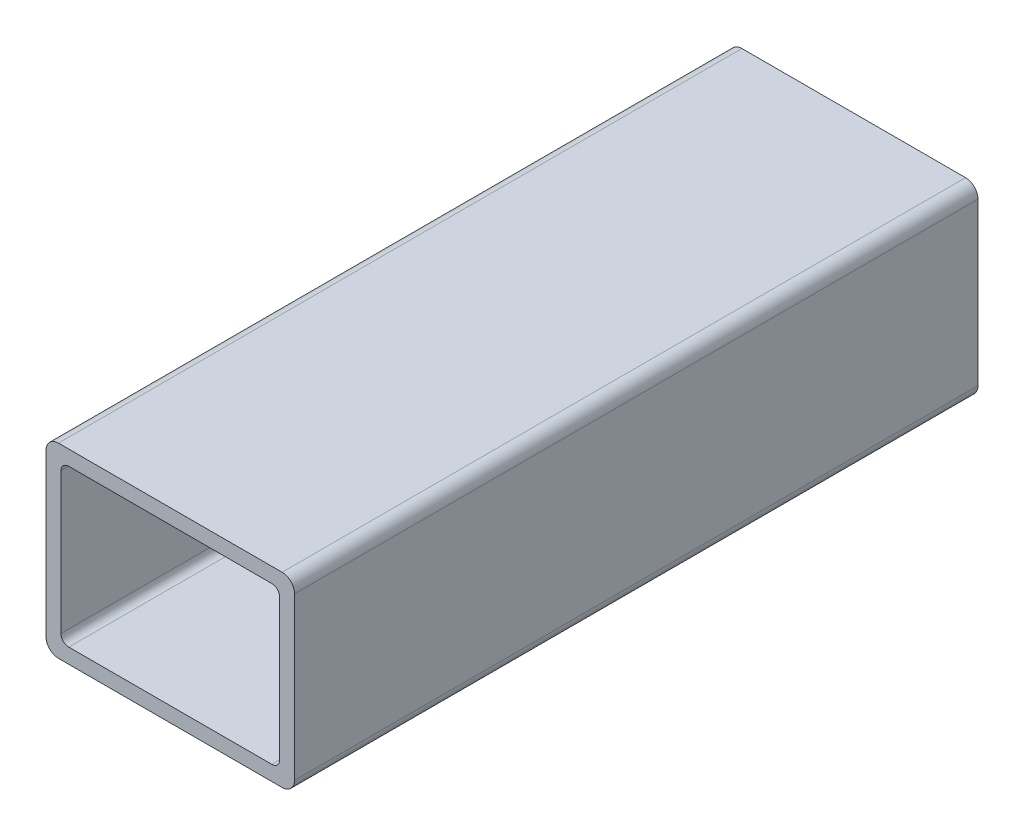
SolidWorks part; units mm, degrees
material "Plain Carbon Steel"
ref_plane "Front" through (0, 0, 0) normal (0, 0, 1) x (1, 0, 0)
ref_plane "Top" through (0, 0, 0) normal (0, 1, 0) x (1, 0, 0)
ref_plane "Right" through (0, 0, 0) normal (1, 0, 0) x (0, 0, -1)
sketch "Sketch1" plane through (0, 0, 0) normal (0, 0, 1) x (1, 0, 0)
  line L0 (-22.352, 0) -> (-25.4, 0) construction
  line L1 (22.86, -19.05) -> (-22.86, -19.05)
  line L2 (25.4, -16.51) -> (25.4, 16.51)
  line L3 (22.86, 19.05) -> (-22.86, 19.05)
  line L4 (-25.4, -16.51) -> (-25.4, 16.51)
  line L5 (25.4, -19.05) -> (-25.4, 19.05) construction
  line L6 (25.4, 19.05) -> (-25.4, -19.05) construction
  line L7 (20.7518, 16.002) -> (-20.7518, 16.002)
  line L8 (22.352, 14.4018) -> (22.352, -14.4018)
  line L9 (20.7518, -16.002) -> (-20.7518, -16.002)
  line L10 (-22.352, 14.4018) -> (-22.352, -14.4018)
  line L11 (22.352, 16.002) -> (-22.352, -16.002) construction
  line L12 (22.352, -16.002) -> (-22.352, 16.002) construction
  line L13 (0, -16.002) -> (0, -19.05) construction
  line L14 (22.352, -14.4018) -> (22.352, -19.05) construction
  line L16 (22.352, -19.05) -> (25.4, -19.05) construction
  arc A0 (-20.7518, -16.002) -> (-22.352, -14.4018) centre (-20.7518, -14.4018) cw
  arc A1 (22.352, -14.4018) -> (20.7518, -16.002) centre (20.7518, -14.4018) cw
  arc A2 (20.7518, 16.002) -> (22.352, 14.4018) centre (20.7518, 14.4018) cw
  arc A3 (-20.7518, 16.002) -> (-22.352, 14.4018) centre (-20.7518, 14.4018) ccw
  arc A4 (22.86, -19.05) -> (25.4, -16.51) centre (22.86, -16.51) ccw
  arc A5 (25.4, 16.51) -> (22.86, 19.05) centre (22.86, 16.51) ccw
  arc A6 (-22.86, 19.05) -> (-25.4, 16.51) centre (-22.86, 16.51) ccw
  arc A7 (-22.86, -19.05) -> (-25.4, -16.51) centre (-22.86, -16.51) cw
  point P0 (0, 0)
  point P6 (0, 0)
  dimension "D2" = 1.6002
  dimension "D3" = 2.54
sketch "Sketch2" plane through (0, 0, 0) normal (1, 0, 0) x (0, 0, -1)
  line L0 (-152.4, 0) -> (152.4, 0) construction
  dimension "Length" = 304.8
ref_plane "Plane1" through (25.4, 0, 0) normal (1, 0, 0) x (0, 0, -1)
sketch "Sketch5" plane through (25.4, 0, 0) normal (1, 0, 0) x (0, 0, -1)
  line L0 (-152.4, 19.05) -> (-152.4, -19.05) construction
  line L1 (152.4, 19.05) -> (152.4, -19.05) construction
sketch "Sketch4" plane through (0, 0, 0) normal (0, 0, 1) x (1, 0, 0)
  line L0 (25.4, -16.51) -> (25.4, 16.51) construction
  line L1 (22.86, 19.05) -> (-22.86, 19.05) construction
  line L2 (-25.4, -16.51) -> (-25.4, 16.51) construction
  line L3 (22.86, -19.05) -> (-22.86, -19.05) construction
  line L4 (22.352, 14.4018) -> (22.352, -14.4018) construction
  line L5 (20.7518, -16.002) -> (-20.7518, -16.002) construction
  line L6 (-22.352, 14.4018) -> (-22.352, -14.4018) construction
  line L7 (20.7518, 16.002) -> (-20.7518, 16.002) construction
  line L8 (25.4, -16.51) -> (25.4, 16.51)
  line L9 (22.86, 19.05) -> (-22.86, 19.05)
  line L10 (-25.4, -16.51) -> (-25.4, 16.51)
  line L11 (22.86, -19.05) -> (-22.86, -19.05)
  line L12 (22.352, 14.4018) -> (22.352, -14.4018)
  line L13 (20.7518, -16.002) -> (-20.7518, -16.002)
  line L14 (-22.352, 14.4018) -> (-22.352, -14.4018)
  line L15 (20.7518, 16.002) -> (-20.7518, 16.002)
  arc A0 (25.4, 16.51) -> (22.86, 19.05) centre (22.86, 16.51) ccw construction
  arc A1 (-22.86, 19.05) -> (-25.4, 16.51) centre (-22.86, 16.51) ccw construction
  arc A2 (-25.4, -16.51) -> (-22.86, -19.05) centre (-22.86, -16.51) ccw construction
  arc A3 (22.86, -19.05) -> (25.4, -16.51) centre (22.86, -16.51) ccw construction
  arc A4 (20.7518, -16.002) -> (22.352, -14.4018) centre (20.7518, -14.4018) ccw construction
  arc A5 (-22.352, -14.4018) -> (-20.7518, -16.002) centre (-20.7518, -14.4018) ccw construction
  arc A6 (-20.7518, 16.002) -> (-22.352, 14.4018) centre (-20.7518, 14.4018) ccw construction
  arc A7 (22.352, 14.4018) -> (20.7518, 16.002) centre (20.7518, 14.4018) ccw construction
  arc A8 (25.4, 16.51) -> (22.86, 19.05) centre (22.86, 16.51) ccw
  arc A9 (-22.86, 19.05) -> (-25.4, 16.51) centre (-22.86, 16.51) ccw
  arc A10 (-25.4, -16.51) -> (-22.86, -19.05) centre (-22.86, -16.51) ccw
  arc A11 (22.86, -19.05) -> (25.4, -16.51) centre (22.86, -16.51) ccw
  arc A12 (20.7518, -16.002) -> (22.352, -14.4018) centre (20.7518, -14.4018) ccw
  arc A13 (-22.352, -14.4018) -> (-20.7518, -16.002) centre (-20.7518, -14.4018) ccw
  arc A14 (-20.7518, 16.002) -> (-22.352, 14.4018) centre (-20.7518, 14.4018) ccw
  arc A15 (22.352, 14.4018) -> (20.7518, 16.002) centre (20.7518, 14.4018) ccw
extrude "Boss-Extrude1" add sketch "Sketch4" along normal blind 139.7
sketch "Sketch6" plane through (0, 19.05, 0) normal (0, 1, 0) x (1, 0, 0)
  line L0 (22.86, -139.7) -> (-22.86, -139.7) construction
  line L8 (0, -139.7) -> (0, 0) construction
  line L9 (22.86, 0) -> (-22.86, 0) construction
equation "\"D3@Sketch1\"=\"Outside Width@Sketch1\"*.05"
equation "\"D2@Sketch1\"=\"D1@Sketch1\"*.05"
